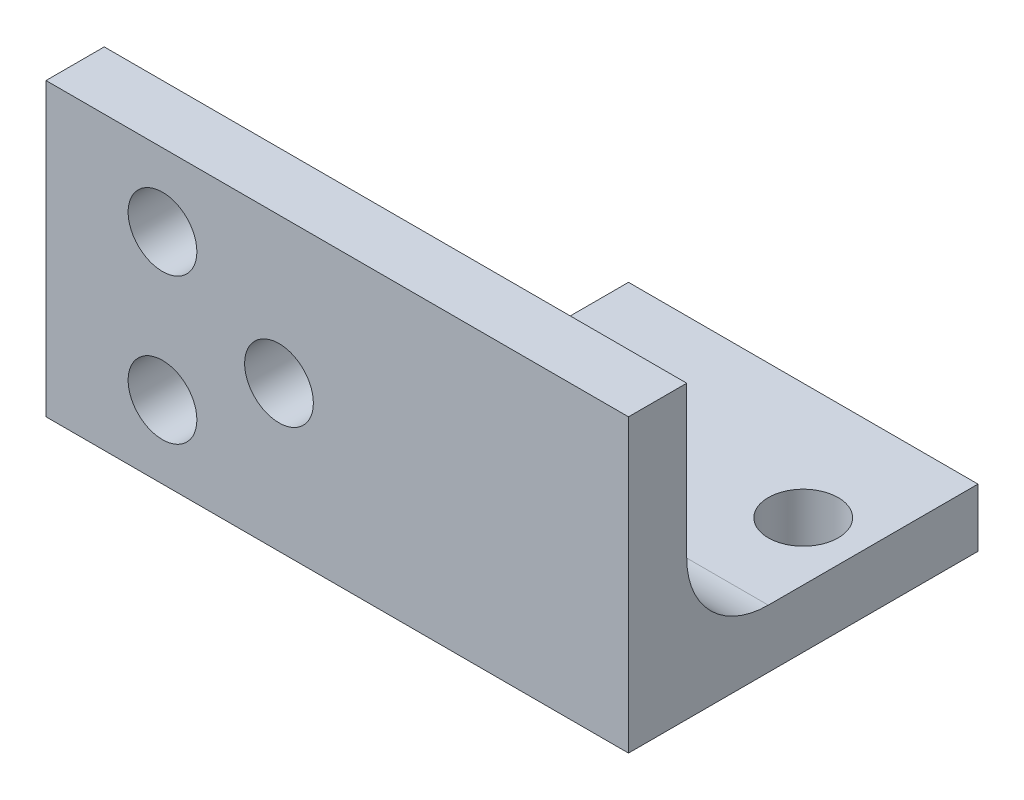
SolidWorks part; units mm, degrees
ref_plane "Alzado" through (0, 0, 0) normal (0, 0, 1) x (1, 0, 0)
ref_plane "Planta" through (0, 0, 0) normal (0, 1, 0) x (1, 0, 0)
ref_plane "Vista lateral" through (0, 0, 0) normal (1, 0, 0) x (0, 0, -1)
sketch "Croquis1" plane through (0, 0, 0) normal (0, 0, 1) x (1, 0, 0)
  line L0 (5, 25) -> (5, 0) construction
  line L1 (0, 0) -> (50, 0)
  line L2 (0, 0) -> (0, 25)
  line L3 (0, 25) -> (50, 25)
  line L4 (50, 0) -> (50, 25)
  line L5 (10, 18.75) -> (10, 6.25) construction
  circle A0 centre (10, 18.75) radius 2.95
  circle A1 centre (10, 6.25) radius 2.95
  circle A2 centre (20, 12.5) radius 2.95
  point P13 (10, 12.5)
  point P14 (0, 12.5)
  dimension "D5" = 10
  dimension "D6" = 10
  dimension "D7" = 5.9
  dimension "D1" = 50
  dimension "D2" = 25
  dimension "D3" = 5
  dimension "D4" = 12.5
extrude "Saliente-Extruir1" add sketch "Croquis1" along normal blind 5
sketch "Croquis2" plane through (0, 0, 0) normal (0, -1, 0) x (1, 0, 0)
  line L0 (50, 5) -> (50, 0) construction
  line L1 (20, 0) -> (50, 0)
  line L2 (20, 0) -> (20, -25)
  line L3 (20, -25) -> (50, -25)
  line L4 (50, 0) -> (50, -25)
  line L5 (0, 0) -> (50, 0) construction
  circle A0 centre (45, -15) radius 3
  circle A1 centre (25, -15) radius 3
  dimension "D1" = 10
  dimension "D3" = 5
  dimension "D4" = 6
  dimension "D6" = 5
  dimension "D2" = 20
  dimension "D5" = 25
extrude "Saliente-Extruir2" add sketch "Croquis2" against normal blind 5
fillet "Redondeo1" radius 7 1 edges at (35, 5, 0)
